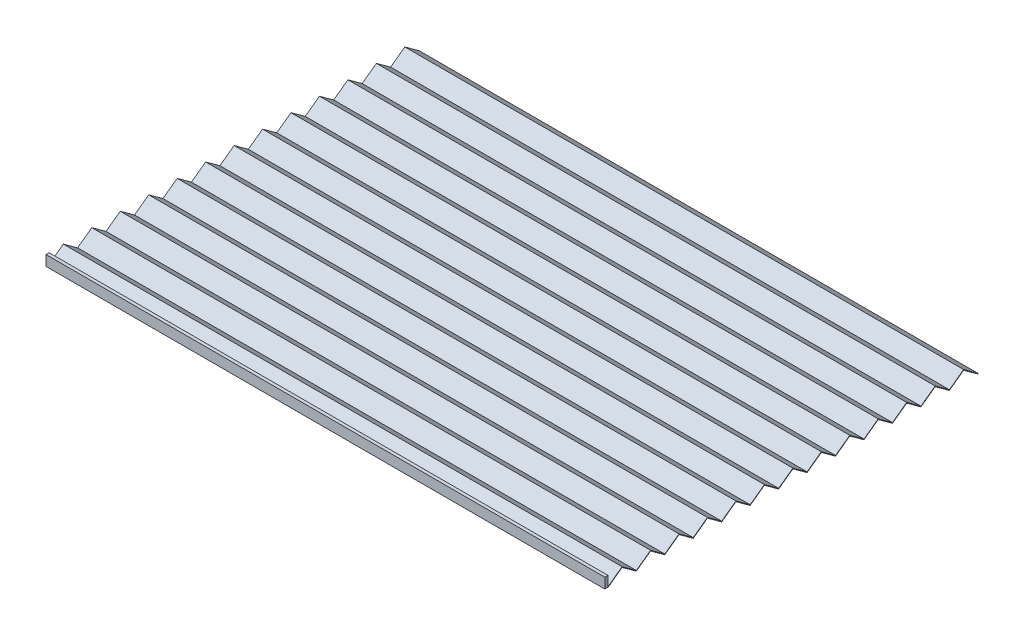
SolidWorks part; units mm, degrees
ref_plane "Front Plane" through (0, 0, 0) normal (0, 0, 1) x (1, 0, 0)
ref_plane "Top Plane" through (0, 0, 0) normal (0, 1, 0) x (1, 0, 0)
ref_plane "Right Plane" through (0, 0, 0) normal (1, 0, 0) x (0, 0, -1)
sketch "Sketch2" plane through (0, 0, 0) normal (0, 0, 1) x (1, 0, 0)
  line L1 (-270, 10) -> (270, 10)
  line L2 (-270, 10) -> (-270, 0)
  line L3 (-270, 0) -> (270, 0)
  line L4 (270, 10) -> (270, 0)
  point P4 (0, 0)
  dimension "D1" = 10
  dimension "D2" = 540
extrude "Boss-Extrude1" add sketch "Sketch2" along normal blind 3
sketch "Sketch3" plane through (270, 0, 0) normal (1, 0, 0) x (0, 0, -1)
  line L0 (0, 10) -> (357.5304, 10) construction
  line L1 (0, 0) -> (357.5304, 0) construction
  line L3 (0, 0) -> (13.7512, 10)
  line L4 (13.7512, 10) -> (27.5023, 0)
  line L5 (27.5023, 0) -> (41.2535, 10)
  line L6 (41.2535, 10) -> (55.0047, 0)
  line L7 (55.0047, 0) -> (68.7558, 10)
  line L8 (68.7558, 10) -> (82.507, 0)
  line L9 (82.507, 0) -> (96.2582, 10)
  line L10 (96.2582, 10) -> (110.0093, 0)
  line L11 (110.0093, 0) -> (123.7605, 10)
  line L12 (123.7605, 10) -> (137.5117, 0)
  line L13 (137.5117, 0) -> (151.2629, 10)
  line L14 (151.2629, 10) -> (165.014, 0)
  line L15 (165.014, 0) -> (178.7652, 10)
  line L16 (178.7652, 10) -> (192.5164, 0)
  line L17 (192.5164, 0) -> (206.2675, 10)
  line L18 (206.2675, 10) -> (220.0187, 0)
  line L20 (220.0187, 0) -> (233.7699, 10)
  line L21 (233.7699, 10) -> (247.521, 0)
  line L22 (247.521, 0) -> (261.2722, 10)
  line L23 (261.2722, 10) -> (275.0234, 0)
  line L24 (275.0234, 0) -> (288.7745, 10)
  line L25 (288.7745, 10) -> (302.5257, 0)
  line L26 (302.5257, 0) -> (316.2769, 10)
  line L27 (316.2769, 10) -> (330.028, 0)
  line L28 (330.028, 0) -> (343.7792, 10)
  line L29 (343.7792, 10) -> (357.5304, 0)
  line L30 (357.5304, 10) -> (357.5304, 0) construction
  line L32 (357.5304, 10) -> (357.5304, 0) construction
extrude "Extrude-Thin1" add sketch "Sketch3" against normal through all thin thin type mid plane wall 0.5
